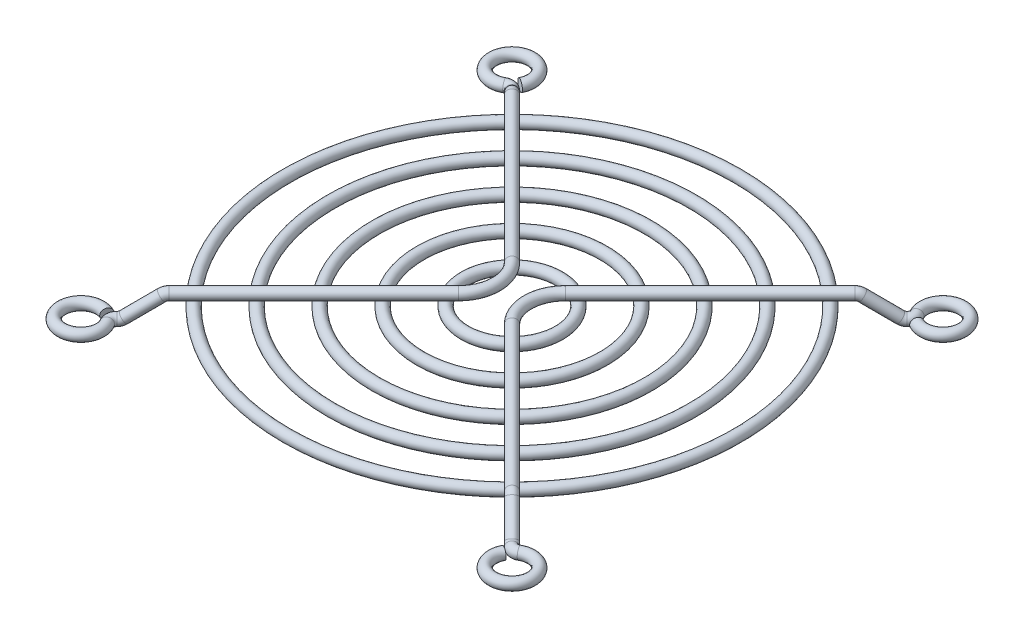
SolidWorks part; units mm, degrees
ref_plane "Front" through (0, 0, 0) normal (0, 0, 1) x (1, 0, 0)
ref_plane "Top" through (0, 0, 0) normal (0, 1, 0) x (1, 0, 0)
ref_plane "Right" through (0, 0, 0) normal (1, 0, 0) x (0, 0, -1)
sketch "Sketch1" plane through (0, 0, 0) normal (0, 0, 1) x (1, 0, 0)
  line L0 (43.835, 0) -> (-43.835, 0) construction
  line L1 (-6.9, 2.8) -> (6.9, 2.8) construction
  line L2 (-38.25, 2.8) -> (38.25, 2.8) construction
  line L3 (0, 2.8) -> (0, 0) construction
  line L4 (-37.35, 2.8) -> (-29.9625, 2.8) construction
  line L5 (-29.9625, 2.8) -> (-22.575, 2.8) construction
  line L6 (-22.575, 2.8) -> (-15.1875, 2.8) construction
  line L7 (-15.1875, 2.8) -> (-7.8, 2.8) construction
  circle A0 centre (-7.8, 4.6) radius 0.9 construction
  circle A1 centre (-7.8, 2.8) radius 0.9
  circle A2 centre (-37.35, 2.8) radius 0.9
  circle A3 centre (-29.9625, 2.8) radius 0.9
  circle A4 centre (-22.575, 2.8) radius 0.9
  circle A5 centre (-15.1875, 2.8) radius 0.9
  point P4 (-7.8, 5.5)
  dimension "D2" = 1.8
  dimension "D1" = 5.5
  dimension "D3" = 13.8
  dimension "D4" = 76.5
revolve "Revolve1" add sketch "Sketch1" angle 360 mid plane about L3
sketch "Sketch2" plane through (0, 0, 0) normal (0, 1, 0) x (1, 0, 0)
  line L0 (-28.461, 28.461) -> (-4.4385, 4.4385)
  line L1 (0, -3.025) -> (0, 3.025) construction
  line L2 (-3.025, 0) -> (3.025, 0) construction
  line L3 (0, 0) -> (-35.75, -35.75) construction
  arc A0 (-4.4385, 4.4385) -> (-2.6, 0) centre (-8.877, 0) cw
  circle A1 centre (-2.6, 0) radius 0.9 construction
  circle A2 centre (0, 0) radius 38.25 construction
  circle A3 centre (-35.75, 35.75) radius 2.3 construction
  circle A4 centre (0, 0) radius 50.5581 construction
  circle A5 centre (-35.75, -35.75) radius 2.3 construction
  circle A6 centre (-35.75, 35.75) radius 4.1 construction
  point P9 (-3.5, 0)
  point P10 (-27.0468, 27.0468)
  dimension "D3" = 1.8
  dimension "D5" = 71.5
  dimension "D6" = 4.6
  dimension "D7" = 1.8
  dimension "D1" = 45
  dimension "D2" = 3.5
  dimension "D4" = 2
sketch "Sketch3" plane through (0, 0, 0) normal (0, 0, 1) x (1, 0, 0)
  circle A0 centre (-2.6, 4.6) radius 0.9
  circle A1 centre (-7.8, 4.6) radius 0.9 construction
sweep "Sweep1" add profiles "Sketch3" path "Sketch2"
ref_plane "Plane1" through (0, 0, 0) normal (0.7071, 0, -0.7071) x (-0.7071, 0, -0.7071)
sketch "Sketch4" plane through (0, 0, 0) normal (0.7071, 0, -0.7071) x (-0.7071, 0, -0.7071)
  line L0 (41.0681, 4.3389) -> (45.5401, 1.1611)
  line L3 (40.25, 3.7) -> (40.25, 5.5) construction
  line L5 (46.3581, 0.9) -> (47.3581, 0.9) construction
  line L10 (46.4581, 0) -> (48.2581, 0) construction
  arc A0 (40.25, 4.6) -> (41.0681, 4.3389) centre (40.25, 3.1877) cw
  arc A1 (45.5401, 1.1611) -> (46.3581, 0.9) centre (46.3581, 2.3123) ccw
  circle A2 centre (47.3581, 0.9) radius 0.9 construction
  point P9 (47.3581, 0)
  dimension "D1" = 1.4123
  dimension "D3" = 1.8
  dimension "D2" = 1
sketch "Sketch5" plane through (-28.461, 0, -28.461) normal (-0.7071, 0, -0.7071) x (-0.7071, 0, 0.7071)
  circle A1 centre (0, 4.6) radius 0.9
  circle A2 centre (0, 4.6) radius 0.9
  dimension "D1" = 0
sweep "Sweep2" add profiles "Sketch5" path "Sketch4"
sketch "Sketch6" plane through (0, 0, 0) normal (0, 1, 0) x (1, 0, 0)
  line L0 (-32.1438, 33.4165) -> (-33.4165, 32.1438) construction
  line L2 (-32.9158, 34.2643) -> (-35.75, 35.75) construction
  arc A0 (-34.169, 32.9678) -> (-32.7802, 32.7802) centre (-33.5977, 31.9626) cw
  arc A2 (-32.9158, 34.2643) -> (-34.169, 32.9678) centre (-35.75, 35.75) ccw
  dimension "D1" = 1.4841
sketch "Sketch7" plane through (-32.7802, 0, -32.7802) normal (-0.7071, 0, -0.7071) x (-0.7071, 0, 0.7071)
  circle A1 centre (0, 0.9) radius 0.9
  circle A2 centre (0, 0.9) radius 0.9
  dimension "D1" = 0
sweep "Sweep3" add profiles "Sketch7" path "Sketch6"
sketch "Sketch8" plane through (0, 0, 0) normal (0, 1, 0) x (1, 0, 0)
  line L0 (-5.0749, 3.8021) -> (-3.8021, 5.0749)
  line L1 (-3.8021, 5.0749) -> (-5.0749, 3.8021) construction
  line L2 (-3.8021, 5.0749) -> (-27.8247, 29.0974) construction
extrude "Cut-Extrude1" cut sketch "Sketch8" against normal through all and the other way through all flip side to cut
pattern_circular "CirPattern1" count 4 over 360 about axis through (0, 0, 0) along (0, 1, 0) of bodies 114
sketch "Sketch9" plane through (0, 0, 0) normal (0, 1, 0) x (1, 0, 0)
  line L0 (-5.0749, 3.8021) -> (-3.8021, 5.0749) construction
  line L1 (-3.8021, -5.0749) -> (-5.0749, -3.8021) construction
  arc A0 (-4.4385, 4.4385) -> (-4.4385, -4.4385) centre (-8.877, 0) cw
sketch "Sketch10" plane through (-4.4385, 0, -4.4385) normal (0.7071, 0, 0.7071) x (0.7071, 0, -0.7071)
  circle A1 centre (0, 4.6) radius 0.9
  circle A2 centre (0, 4.6) radius 0.9
  dimension "D1" = 0
sweep "Sweep4" add profiles "Sketch10" path "Sketch9"
sketch "Sketch11" plane through (0, 0, 0) normal (0, 1, 0) x (1, 0, 0)
  line L0 (3.8021, 5.0749) -> (5.0749, 3.8021) construction
  line L1 (5.0749, -3.8021) -> (3.8021, -5.0749) construction
  arc A0 (4.4385, 4.4385) -> (4.4385, -4.4385) centre (8.877, 0) ccw
sketch "Sketch12" plane through (4.4385, 0, -4.4385) normal (-0.7071, 0, 0.7071) x (0.7071, 0, 0.7071)
  circle A1 centre (0, 4.6) radius 0.9
  circle A2 centre (0, 4.6) radius 0.9
  dimension "D1" = 0
sweep "Sweep5" add profiles "Sketch12" path "Sketch11"
sketch "Sketch13" plane through (0, 0, 0) normal (0, 0, 1) x (1, 0, 0)
  point P0 (-39.5796, 0)
  dimension "D1" = 39.5796
sketch "Sketch14" plane through (0, 0, 0) normal (0, 1, 0) x (1, 0, 0)
  line L0 (-40, 40) -> (40, -40) construction
  line L1 (-40, 40) -> (40, 40)
  line L2 (-40, 40) -> (-40, -40)
  line L3 (-40, -40) -> (40, -40)
  line L4 (40, 40) -> (40, -40)
  circle A0 centre (0, 0) radius 38.25 construction
  circle A1 centre (0, 0) radius 36.45 construction
  point P4 (-38.25, 0)
  point P5 (-36.45, 0)
  dimension "D1" = 80
